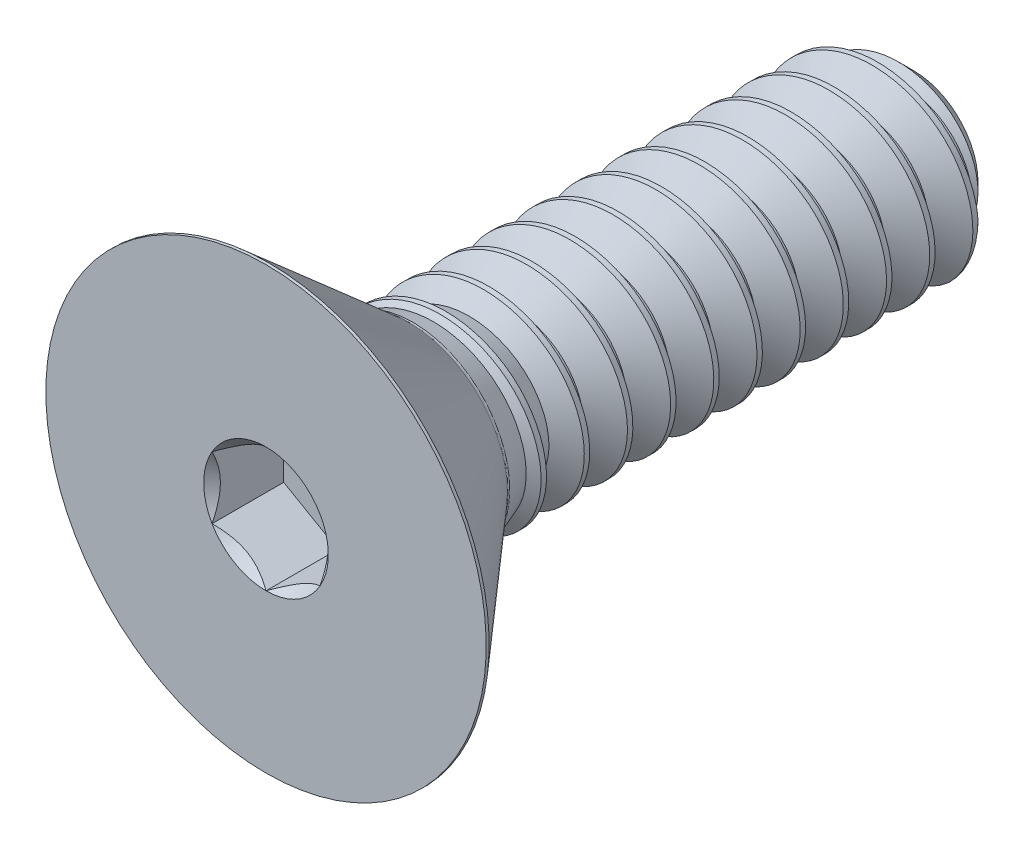
SolidWorks part; units mm, degrees
ref_plane "Front Plane" through (0, 0, 0) normal (0, 0, 1) x (1, 0, 0)
ref_plane "Top Plane" through (0, 0, 0) normal (0, 1, 0) x (1, 0, 0)
ref_plane "Right Plane" through (0, 0, 0) normal (1, 0, 0) x (0, 0, -1)
sketch "Sketch1" plane through (0, 0, 0) normal (1, 0, 0) x (0, 0, -1)
  line L0 (-4.7625, 0) -> (4.7625, 0) construction
  line L1 (-4.7625, 0) -> (-4.7625, 3.2385)
  line L2 (-4.7625, 3.2385) -> (-4.7203, 3.2385)
  line L3 (-4.7203, 3.2385) -> (-2.6543, 1.4425)
  line L4 (-4.7203, -3.2385) -> (-2.6543, -1.4425)
  line L5 (4.7625, 0) -> (4.7625, 1.4224)
  line L6 (4.7625, 1.4224) -> (-2.6543, 1.4224)
  line L7 (4.2862, 1.4224) -> (4.7625, 0.9461)
  line L8 (4.7228, 1.4911) -> (5.0403, 0.9412) construction
  line L9 (5.0403, 0.9412) -> (5.3578, 1.4911) construction
  line L10 (5.3578, 1.4911) -> (4.7228, 1.4911) construction
  line L11 (4.7427, 1.4568) -> (5.338, 1.4568)
  line L12 (5.338, 1.4568) -> (5.08, 1.01)
  line L13 (5.08, 1.01) -> (5.0006, 1.01)
  line L14 (5.0006, 1.01) -> (4.7427, 1.4568)
  line L15 (5.0403, 1.01) -> (5.0403, 0.9412) construction
  line L16 (4.7625, 1.4224) -> (5.3181, 1.4224) construction
  line L17 (5.0403, 1.4911) -> (5.0403, 1.4224) construction
  line L18 (4.7625, -1.4224) -> (-2.6543, -1.4224)
  arc A0 (-2.6543, 1.4425) -> (-2.6005, 1.4224) centre (-2.6005, 1.5044) ccw
  point P2 (0, 0)
  point P23 (-3.7084, 0)
  point P27 (5.0403, 1.4568)
  point P30 (3.81, -1.4224)
  point P34 (-4.7203, -3.2385)
  dimension "Length" = 9.525
  dimension "Head Height" = 2.1082
  dimension "Head Diameter" = 6.477
  dimension "Countersink Angle" = 82
  dimension "Thread Diameter" = 2.8448
  dimension "D2" = 0.0422
  dimension "Pitch" = 0.635
  dimension "D4" = 0.0794
  dimension "D3" = 45
  dimension "D5" = 0.4763
  dimension "D6" = 1.0541
  dimension "D1" = 0.9525
sketch "Sketch2" plane through (0, 0, 0) normal (0, 0, 1) x (1, 0, 0)
  line L1 (0, 0.9165) -> (-0.7938, 0.4583)
  line L2 (-0.7938, 0.4583) -> (-0.7938, -0.4583)
  line L3 (-0.7938, -0.4583) -> (0, -0.9165)
  line L4 (0, -0.9165) -> (0.7937, -0.4583)
  line L5 (0.7937, -0.4583) -> (0.7937, 0.4583)
  line L6 (0.7937, 0.4583) -> (0, 0.9165)
  circle A0 centre (0, 0) radius 0.7938 construction
  dimension "Drive Size" = 1.5875
sketch "Sketch11" plane through (0, 0, 0) normal (1, 0, 0) x (0, 0, -1)
  line L0 (-4.7203, 3.2385) -> (-2.6543, 1.4425) construction
  line L1 (-4.7625, 0) -> (-4.7625, 3.2385) construction
  line L2 (-4.7203, 3.2385) -> (-2.6543, 1.4425)
  line L3 (-4.7625, 0) -> (-4.7625, 3.2385)
  line L4 (-4.7625, 3.2385) -> (-4.7203, 3.2385) construction
  line L5 (-4.7625, 3.2385) -> (-4.7203, 3.2385)
  line L6 (-2.6005, 1.4224) -> (4.2862, 1.4224)
  line L7 (4.2862, 1.4224) -> (4.7625, 0.9461)
  line L8 (4.7625, 0.9461) -> (4.7625, 0)
  line L9 (4.7625, 0) -> (-4.7625, 0)
  arc A0 (-2.6543, 1.4425) -> (-2.6005, 1.4224) centre (-2.6005, 1.5044) ccw construction
  arc A1 (-2.6543, 1.4425) -> (-2.6005, 1.4224) centre (-2.6005, 1.5044) ccw
revolve "Revolve1" add sketch "Sketch11" angle 360 about L9
sketch "Sketch9" plane through (0, 0, 4.7625) normal (0, 0, 1) x (1, 0, 0)
  line L0 (0.7937, -0.4583) -> (0.7937, 0.4583) construction
  line L1 (0, -0.9165) -> (0.7937, -0.4583) construction
  line L2 (-0.7938, -0.4583) -> (0, -0.9165) construction
  line L3 (-0.7938, 0.4583) -> (-0.7938, -0.4583) construction
  line L4 (0, 0.9165) -> (-0.7938, 0.4583) construction
  line L5 (0.7937, 0.4583) -> (0, 0.9165) construction
  line L6 (0.7937, -0.4583) -> (0.7937, 0.4583)
  line L7 (0, -0.9165) -> (0.7937, -0.4583)
  line L8 (-0.7938, -0.4583) -> (0, -0.9165)
  line L9 (-0.7938, 0.4583) -> (-0.7938, -0.4583)
  line L10 (0, 0.9165) -> (-0.7938, 0.4583)
  line L11 (0.7937, 0.4583) -> (0, 0.9165)
sketch "Sketch10" plane through (0, 0, 4.7625) normal (0, 0, 1) x (1, 0, 0)
  circle A0 centre (0, 0) radius 0.9165
extrude "Cut-Extrude2" cut sketch "Sketch10" against normal up to vertex (1.0541 mm away) draft 45 up to point (0, 0, 3.7084)
extrude "Cut-Extrude1" cut sketch "Sketch9" against normal up to vertex (1.0541 mm away) up to point (0, 0, 3.7084)
ref_plane "Plane1" through (0, 0, 2.6005) normal (0, 0, 1) x (1, 0, 0)
split "Split1" trim tools "Plane1" bodies to split 111 resulting bodies 105 106
sketch "Sketch3" plane through (0, 0, -4.7625) normal (0, 0, -1) x (-1, 0, 0)
  circle A0 centre (0, 0) radius 1.4224 construction
  circle A1 centre (0, 0) radius 1.4224
curve "Helix/Spiral1" pitch 0.635 height 9.525 turns 15
sketch "Sketch4" plane through (0, 0, 0) normal (1, 0, 0) x (0, 0, -1)
  line L0 (4.7427, 1.4568) -> (5.338, 1.4568) construction
  line L1 (5.0006, 1.01) -> (4.7427, 1.4568) construction
  line L2 (5.08, 1.01) -> (5.0006, 1.01) construction
  line L3 (5.338, 1.4568) -> (5.08, 1.01) construction
  line L4 (4.7427, 1.4568) -> (5.338, 1.4568)
  line L5 (5.0006, 1.01) -> (4.7427, 1.4568)
  line L6 (5.08, 1.01) -> (5.0006, 1.01)
  line L7 (5.338, 1.4568) -> (5.08, 1.01)
sweep "Cut-Sweep1" cut profiles "Sketch4" path "Helix/Spiral1" align with end faces yes
sketch "Sketch7" plane through (0, 0, 2.6005) normal (0, 0, 1) x (1, 0, 0)
  circle A0 centre (0, 0) radius 1.4224
extrude "Boss-Extrude2" add sketch "Sketch7" against normal up to next (7.363 mm away) draft 20
equation "\"D2@Sketch1\"=\"Head Height@Sketch1\"/50"
equation "\"D4@Sketch1\" = \"Pitch@Sketch1\" / 8"
equation "\"D5@Sketch1\"=\"Pitch@Sketch1\"*0.75"
equation "\"D4@Helix/Spiral1\"=\"Pitch@Sketch1\""
equation "\"D3@Helix/Spiral1\"=\"Length@Sketch1\""
equation "\"D6@Sketch1\"=\"Head Height@Sketch1\"/2"
equation "\"D1@Sketch1\"=\"Pitch@Sketch1\"*1.5"
